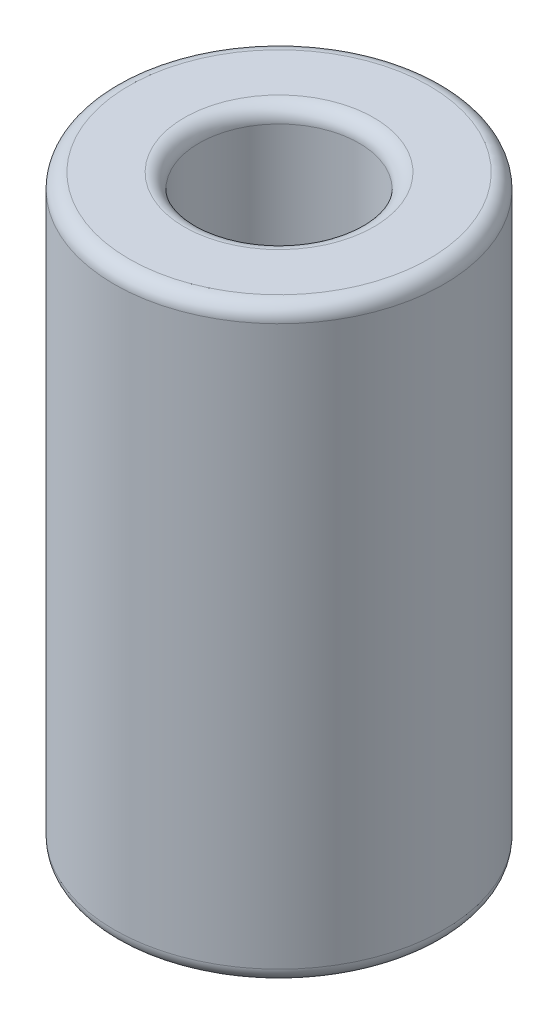
SolidWorks part; units mm, degrees
ref_plane "Front Plane" through (0, 0, 0) normal (0, 0, 1) x (1, 0, 0)
ref_plane "Top Plane" through (0, 0, 0) normal (0, 1, 0) x (1, 0, 0)
ref_plane "Right Plane" through (0, 0, 0) normal (1, 0, 0) x (0, 0, -1)
sketch "Sketch1" plane through (0, 0, 0) normal (0, 1, 0) x (1, 0, 0)
  circle A0 centre (0, 0) radius 2.159
  circle A1 centre (0, 0) radius 4.445
  dimension "D1" = 4.318
  dimension "D2" = 8.89
extrude "Boss-Extrude1" add sketch "Sketch1" along normal blind 15.875
fillet "Fillet1" radius 0.3969 4 edges at (0, 0, 2.159) (0, 0, 4.445) (0, 15.875, 2.159) (0, 15.875, 4.445)
